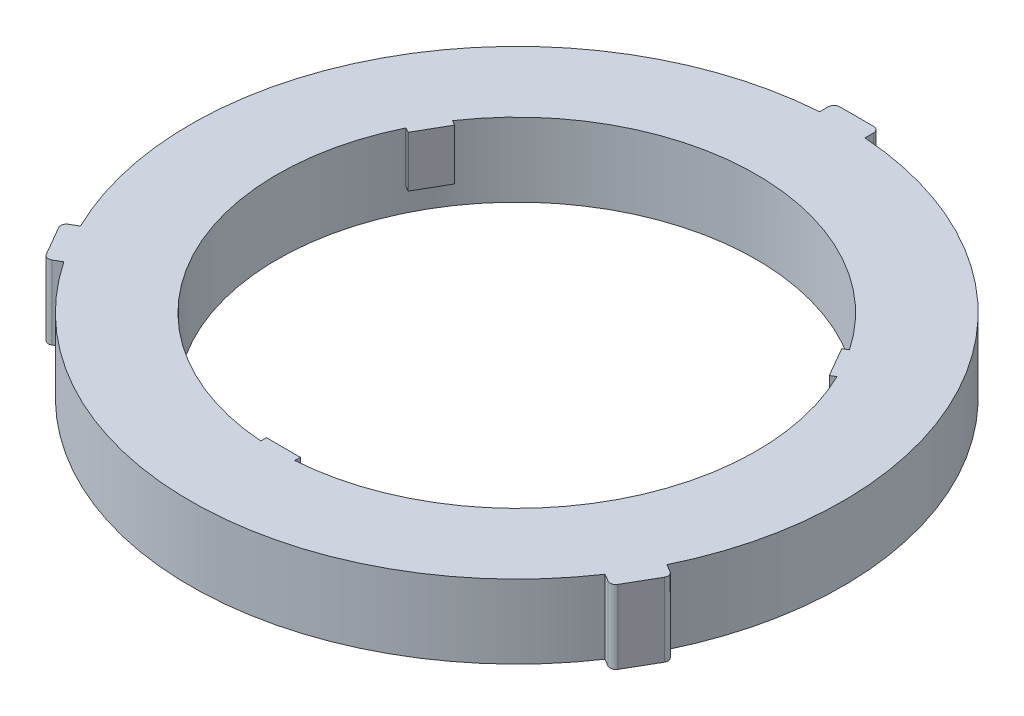
SolidWorks part; units mm, degrees
note: The reader was unsure of these and kept them because the rebuilt part matched: shared geometry of "Sketch1<5>".
ref_plane "Front Plane" through (0, 0, 0) normal (0, 0, 1) x (1, 0, 0)
ref_plane "Top Plane" through (0, 0, 0) normal (0, 1, 0) x (1, 0, 0)
ref_plane "Right Plane" through (0, 0, 0) normal (1, 0, 0) x (0, 0, -1)
sketch "Sketch1" plane through (0, 0, 0) normal (0, 1, 0) x (1, 0, 0)
  line L53 (25.5085, -12.4179) -> (23.5085, -15.8821)
  line L54 (-2, 28.3) -> (2, 28.3)
  line L62 (-2, 28.3) -> (-2, 29.3)
  line L75 (-2, 29.3) -> (2, 29.3)
  line L80 (2, 28.3) -> (2, 29.3)
  line L81 (-2, 28.3) -> (2, 29.3) construction
  line L90 (-2, 29.3) -> (-2, 30)
  line L91 (-2, 30) -> (2, 30)
  line L92 (2, 30) -> (2, 29.3)
  line L93 (-2, 29.3) -> (2, 28.3) construction
  line L99 (-1.5, -21.7) -> (1.5, -21.7)
  line L100 (25.5085, -12.4179) -> (26.3745, -12.9179)
  line L101 (26.3745, -12.9179) -> (24.3745, -16.3821)
  line L102 (23.5085, -15.8821) -> (24.3745, -16.3821)
  line L103 (26.3745, -12.9179) -> (26.9808, -13.2679)
  line L104 (26.9808, -13.2679) -> (24.9808, -16.7321)
  line L105 (-1.5, -21.7) -> (-1.5, -20.6)
  line L106 (-1.5, -20.6) -> (1.5, -20.6)
  line L107 (1.5, -21.7) -> (1.5, -20.6)
  line L108 (-1.5, -21.7) -> (1.5, -20.6) construction
  line L109 (-1.5, -20.6) -> (1.5, -21.7) construction
  line L116 (24.9808, -16.7321) -> (24.3745, -16.3821)
  line L117 (25.5085, -12.4179) -> (20.4678, -9.5077)
  line L123 (18.4678, -12.9718) -> (23.5085, -15.8821)
  line L124 (25.5085, -12.4179) -> (24.3745, -16.3821) construction
  line L125 (26.3745, -12.9179) -> (23.5085, -15.8821) construction
  line L126 (-23.5085, -15.8821) -> (-25.5085, -12.4179)
  line L127 (-23.5085, -15.8821) -> (-24.3745, -16.3821)
  line L129 (-2, 28.3) -> (-2, 22.4794)
  line L130 (-2, 22.4794) -> (2, 22.4794)
  line L131 (2, 22.4794) -> (2, 28.3)
  line L138 (-24.3745, -16.3821) -> (-26.3745, -12.9179)
  line L139 (-25.5085, -12.4179) -> (-26.3745, -12.9179)
  line L140 (-24.3745, -16.3821) -> (-24.9808, -16.7321)
  line L141 (-24.9808, -16.7321) -> (-26.9808, -13.2679)
  line L142 (-26.9808, -13.2679) -> (-26.3745, -12.9179)
  line L143 (-23.5085, -15.8821) -> (-18.4678, -12.9718)
  line L144 (-20.4678, -9.5077) -> (-25.5085, -12.4179)
  line L145 (-23.5085, -15.8821) -> (-26.3745, -12.9179) construction
  line L146 (-24.3745, -16.3821) -> (-25.5085, -12.4179) construction
  line L147 (-18.0428, 12.149) -> (-19.5428, 9.551)
  line L148 (-18.0428, 12.149) -> (-17.0901, 11.599)
  line L149 (-17.0901, 11.599) -> (-18.5901, 9.001)
  line L150 (-19.5428, 9.551) -> (-18.5901, 9.001)
  line L151 (-18.0428, 12.149) -> (-18.5901, 9.001) construction
  line L152 (-17.0901, 11.599) -> (-19.5428, 9.551) construction
  line L153 (19.5428, 9.551) -> (18.0428, 12.149)
  line L154 (19.5428, 9.551) -> (18.5901, 9.001)
  line L155 (18.5901, 9.001) -> (17.0901, 11.599)
  line L156 (18.0428, 12.149) -> (17.0901, 11.599)
  line L157 (19.5428, 9.551) -> (17.0901, 11.599) construction
  line L158 (18.5901, 9.001) -> (18.0428, 12.149) construction
  circle A6 centre (0, 0) radius 21.15
  circle A7 centre (0, 0) radius 28.8
  circle A8 centre (0, 0) radius 21.15
  circle A9 centre (0, 0) radius 21.15
  circle A10 centre (0, 0) radius 21.15
  circle A11 centre (0, 0) radius 21.15
  circle A12 centre (0, 0) radius 21.15
  point P3 (0, 28.8)
  point P8 (0, -21.15)
  point P11 (0, -21.15)
  point P16 (24.9415, -14.4)
  point P28 (-18.3164, 10.575)
  point P30 (-18.3164, 10.575)
  point P37 (-24.9415, -14.4)
  point P47 (18.3164, 10.575)
  point P50 (18.3164, 10.575)
  point P55 (0, 0)
  dimension "D1" = 42.3
  dimension "D2" = 4
  dimension "D3" = 1
  dimension "D4" = 3
  dimension "D8" = 57.6
  dimension "D5" = 1.1
  dimension "D6" = 0.7
  dimension "D7" = 3
  dimension "D9" = 3
extrude "Boss-Extrude1" add sketch "Sketch1" along normal blind 6.5
fillet "Fillet1" radius 0.5 6 edges at (-2, 3.25, -30) (2, 3.25, -30) (26.9808, 3.25, 13.2679) (24.9808, 3.25, 16.7321) (-26.9808, 3.25, 13.2679) (-24.9808, 3.25, 16.7321)
extrude "Cut-Extrude1" cut sketch "Sketch1<5>" along normal blind 2 contours L105 A6 L107 L106 | L148 A6 L150 L149 | L154 A6 L156 L155
sketch "Sketch1<5>" plane through (0, 0, 0) normal (0, 1, 0) x (1, 0, 0) same geometry as "Sketch1"
